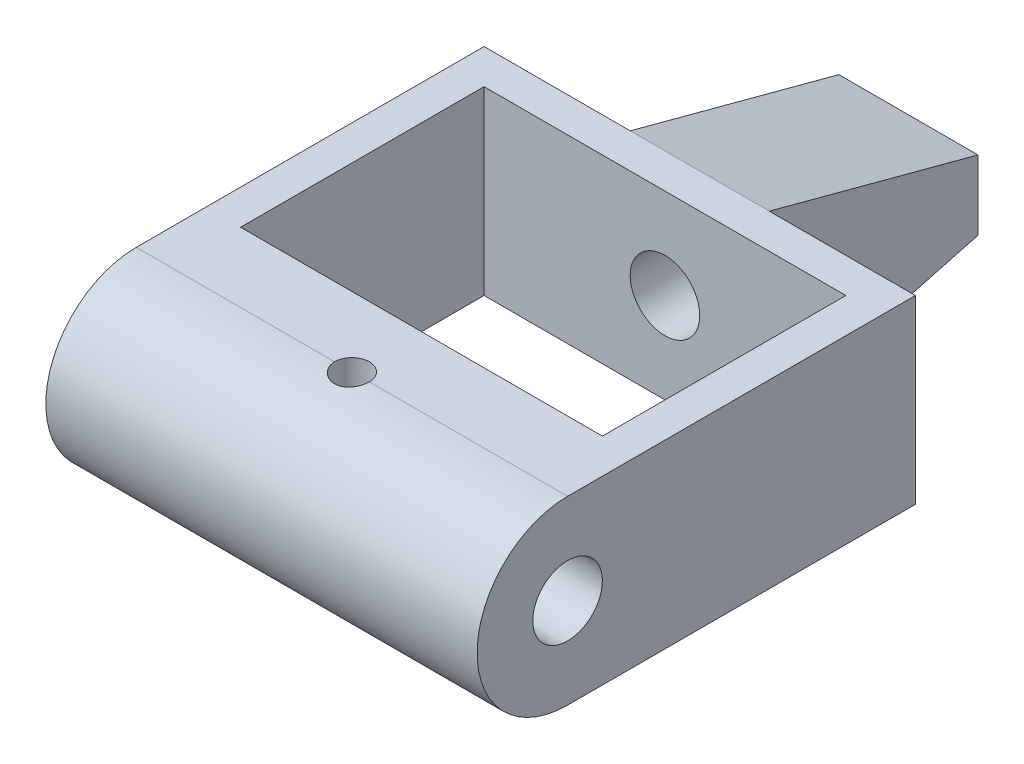
SolidWorks part; units mm, degrees
ref_plane "Alzado" through (0, 0, 0) normal (0, 0, 1) x (1, 0, 0)
ref_plane "Planta" through (0, 0, 0) normal (0, 1, 0) x (1, 0, 0)
ref_plane "Vista lateral" through (0, 0, 0) normal (1, 0, 0) x (0, 0, -1)
sketch "Croquis1" plane through (0, 0, 0) normal (1, 0, 0) x (0, 0, -1)
  circle A0 centre (0, 0) radius 13
extrude "Saliente-Extruir1" add sketch "Croquis1" along normal blind 62
sketch "Croquis2" plane through (62, 0, 0) normal (1, 0, 0) x (0, 0, -1)
  circle A0 centre (0, 0) radius 5
extrude "Cortar-Extruir1" cut sketch "Croquis2" against normal blind 62
sketch "Croquis3" plane through (0, 0, 0) normal (0, 1, 0) x (1, 0, 0)
  line L0 (0, 0) -> (62, 0) construction
  line L1 (62, -13) -> (62, 13) construction
  circle A0 centre (31, 0) radius 2.5
extrude "Cortar-Extruir2" cut sketch "Croquis3" against normal blind 62 and the other way blind 62
sketch "Croquis4" plane through (62, 0, 0) normal (1, 0, 0) x (0, 0, -1)
  line L0 (0, 13) -> (50, 13)
  line L1 (0, -13) -> (50, -13)
  line L2 (50, 0) -> (80, 0)
  line L3 (80, 0) -> (80, 5)
  line L4 (80, 0) -> (80, -5)
  line L5 (80, 5) -> (50, 13)
  line L6 (80, -5) -> (50, -13)
  circle A0 centre (0, 0) radius 13 construction
  arc A1 (0, -13) -> (0, 13) centre (0, 0) ccw
  circle M6 centre (0, 0) radius 13
  dimension "D1" = 50
  dimension "D2" = 50
extrude "Saliente-Extruir2" add sketch "Croquis4" against normal blind 62 contours L6 L4 L3 L5 L0 L1 M6 region at (62, 0, -41.2409)
sketch "Croquis5" plane through (0, 13, 0) normal (0, 1, 0) x (1, 0, 0)
  line L0 (0, 50) -> (5, 50)
  line L1 (0, 50) -> (62, 50) construction
  line L2 (5, 50) -> (5, 45)
  line L3 (62, 0) -> (57, 0)
  line L4 (33.5, 0) -> (62, 0) construction
  line L5 (57, 0) -> (57, 10)
  line L7 (57, 10) -> (5, 10)
  line L8 (57, 10) -> (57, 45)
  line L9 (57, 45) -> (5, 45)
  line L10 (5, 10) -> (5, 45)
extrude "Cortar-Extruir4" cut sketch "Croquis5" against normal blind 62 contours L10 L7 L8 L9 region at (31, 13, -27.5)
sketch "Croquis6" plane through (0, 13, 0) normal (0, 1, 0) x (1, 0, 0)
  circle A0 centre (31, 0) radius 2.5
extrude "Cortar-Extruir5" cut sketch "Croquis6" against normal blind 62
sketch "Croquis7" plane through (0, 0, -80) normal (0, 0, -1) x (-1, 0, 0)
  line L0 (-62, 0) -> (0, 0) construction
  line L1 (-62, 5) -> (-62, -5) construction
  circle A0 centre (-31, 0) radius 5
extrude "Cortar-Extruir6" cut sketch "Croquis7" against normal blind 62
sketch "Croquis8" plane through (0, 0, 0) normal (0, 1, 0) x (1, 0, 0)
  line L1 (0, 80) -> (31, 80) construction
  line L3 (31, 80) -> (62, 80) construction
  line L4 (41, 80) -> (62, 50)
  line L5 (21, 80) -> (0, 50)
  line L6 (0, 50) -> (21, 50)
  line L7 (21, 80) -> (21, 50)
  line L8 (41, 80) -> (41, 50)
  line L9 (41, 50) -> (62, 50)
  line L11 (21, 50) -> (0, 50)
  line L12 (21, 50) -> (21, 80)
  line L13 (21, 80) -> (0, 80)
  line L14 (0, 50) -> (0, 80)
  line L15 (41, 50) -> (62, 50)
  line L16 (41, 50) -> (41, 80)
  line L17 (41, 80) -> (62, 80)
  line L18 (62, 50) -> (62, 80)
extrude "Cortar-Extruir8" cut sketch "Croquis8" against normal blind 62 and the other way blind 62 contours L14 L5 L13 | L4 L18 L17 | L8 L9 L4 | L7 L5 L6 region at (55, 0, -70) region at (48, 0, -60) region at (14, 0, -60) region at (7, 0, -70)
sketch "Croquis9" plane through (0, 0, -80) normal (0, 0, -1) x (-1, 0, 0)
  point P0 (-31, 0)
  point P1 (-5.8591, 18.7673)
